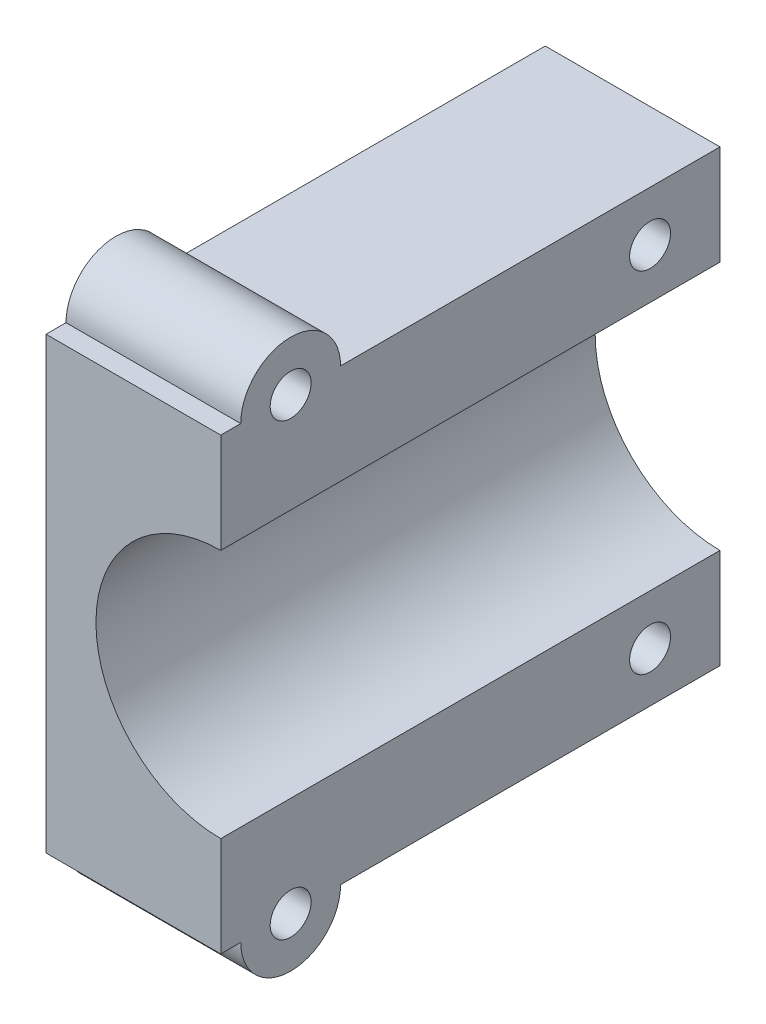
SolidWorks part; units mm, degrees
material "PLA"
ref_plane "Front Plane" through (0, 0, 0) normal (0, 0, 1) x (1, 0, 0)
ref_plane "Top Plane" through (0, 0, 0) normal (0, 1, 0) x (1, 0, 0)
ref_plane "Right Plane" through (0, 0, 0) normal (1, 0, 0) x (0, 0, -1)
sketch "Sketch1" plane through (0, 0, 0) normal (0, 0, 1) x (1, 0, 0)
  line L0 (-17.5, 22.5) -> (-17.5, 0)
  line L1 (55, 0) -> (-55, 0) construction
  line L2 (-17.5, 0) -> (17.5, 0)
  line L3 (17.5, 0) -> (17.5, 22.5)
  line L4 (-17.5, 22.5) -> (-12.5, 22.5)
  line L5 (17.5, 22.5) -> (12.5, 22.5)
  line L6 (0, -44.7868) -> (0, 44.7868) construction
  arc A0 (-12.5, 22.5) -> (12.5, 22.5) centre (0, 22.5) ccw
  dimension "D1" = 12.5
  dimension "D2" = 22.5
  dimension "D3" = 5
extrude "Boss-Extrude1" add sketch "Sketch1" along normal mid plane 50
sketch "Construct1" plane through (0, 0, 0) normal (0, 1, 0) x (1, 0, 0)
  line L0 (17.5, 0) -> (43.4808, -15) construction
  line L1 (-44.2539, 0) -> (44.2539, 0) construction
  line L2 (34.7051, -0.1998) -> (26.2756, -14.8002) construction
  line L3 (17.5, -25) -> (17.5, 25) construction
  point P6 (30.4904, -7.5)
  point P7 (30.4904, -7.5)
  dimension "D1" = 30
  dimension "D2" = 15
ref_plane "LegBuildPlane" through (26.1154, 0, 15.0777) normal (0.866, 0, 0.5) x (0.5, 0, -0.866)
sketch "Sketch5" plane through (26.1154, 0, 15.0777) normal (0.866, 0, 0.5) x (0.5, 0, -0.866)
  line L0 (-8.7, 22.5) -> (-3.75, 22.5)
  line L1 (21.25, 22.5) -> (26.2, 22.5)
  line L2 (17.1795, 0) -> (0.3205, 0) construction
  arc A0 (-3.75, 22.5) -> (21.25, 22.5) centre (8.75, 22.5) ccw
  arc A1 (-8.7, 22.5) -> (26.2, 22.5) centre (8.75, 22.5) ccw
  point P9 (8.75, 0)
  dimension "D1" = 17.45
  dimension "D2" = 12.5
  dimension "D3" = 22.5
  dimension "D4" = 0
extrude "Boss-Extrude2" add sketch "Sketch5" against normal up to surface and the other way blind 30 up to face at (17.5, 11.25, 0)
sketch "Sketch9" plane through (-17.5, 0, 0) normal (-1, 0, 0) x (0, 0, 1)
  line L2 (55, 0) -> (-55, 0) construction
  line L3 (-25, 22.5) -> (-25, 0) construction
  circle A0 centre (-18, 5) radius 2.05
  dimension "D1" = 4.1
  dimension "D2" = 5
  dimension "D3" = 7
extrude "Cut-Extrude3" cut sketch "Sketch9" against normal up to surface (35 mm away) up to face at (17.5, 12.0917, 0)
sketch "Construct2" plane through (0, 22.5, 0) normal (0, 1, 0) x (1, 0, 0)
  line L0 (20.0981, -15.9338) -> (32.5981, 5.7169) construction
  line L2 (50.2211, -33.3253) -> (17.5, -14.4338) construction
  line L3 (62.7211, -11.6747) -> (17.5, 14.4338) construction
  line L4 (17.5, 0) -> (26.3481, -5.1084) construction
  line L11 (-44.2539, 0) -> (44.2539, 0) construction
  dimension "D1" = 3
  dimension "D2" = 90
ref_plane "LegBuildPlane2" through (21.9731, 0, 12.6862) normal (0.866, 0, 0.5) x (0.5, 0, -0.866)
sketch "Sketch12" plane through (21.9731, 0, 12.6862) normal (0.866, 0, 0.5) x (0.5, 0, -0.866)
  line L0 (-3.75, 22.5) -> (21.25, 22.5)
  arc A0 (-3.75, 22.5) -> (21.25, 22.5) centre (8.75, 22.5) ccw
extrude "Boss-Extrude5" add sketch "Sketch12" against normal up to surface (17.4338 mm away) up to face at (17.5, 16.25, 0)
mirror "Mirror1" about plane through (17.5, 22.5, 25) normal (0, -1, 0) of "Boss-Extrude2", "Boss-Extrude1", "Cut-Extrude3", "Boss-Extrude5"
sketch "Sketch13" plane through (0, 0, 0) normal (0, 1, 0) x (1, 0, 0)
  line L0 (17.5, 0) -> (43.4808, -15) construction
  line L1 (47.7461, -37.6121) -> (65.1961, -7.3879) construction
  circle A0 centre (43.4808, -15) radius 1.55
  dimension "D2" = 3.1
  dimension "D1" = 15
extrude "Cut-Extrude4" cut sketch "Sketch13" along normal through all
sketch "Sketch16" plane through (0, 0, 0) normal (1, 0, 0) x (0, 0, -1)
  line L1 (25, 45) -> (-38, 45)
  line L2 (25, 45) -> (25, 0)
  line L3 (25, 0) -> (-38, 0)
  line L4 (-38, 45) -> (-38, 0)
  line L7 (55, 0) -> (-55, 0) construction
  line L8 (0, 44.2539) -> (0, -44.2539) construction
  dimension "D1" = 38
extrude "Cut-Extrude5" cut sketch "Sketch16" along normal up to surface (83.8953 mm away) up to face at (65.1961, 22.5, 7.3879)
sketch "Sketch17" plane through (-17.5, 0, 0) normal (-1, 0, 0) x (0, 0, 1)
  line L0 (55, 0) -> (-55, 0) construction
  line L1 (13, 0) -> (23, 0)
  arc A0 (13, 0) -> (23, 0) centre (18, 0) ccw
  circle A1 centre (-18, 5) radius 2.05 construction
  dimension "D2" = 5
  dimension "D1" = 36
extrude "Boss-Extrude6" add sketch "Sketch17" against normal blind 17.5
sketch "Sketch18" plane through (-17.5, 0, 0) normal (-1, 0, 0) x (0, 0, 1)
  circle A0 centre (18, 0) radius 2.05
  dimension "D1" = 4.1
extrude "Cut-Extrude6" cut sketch "Sketch18" against normal up to surface (17.5 mm away) up to face at (0, 5, -15.95)
ref_plane "HolePlane" through (0, 22.5, 0) normal (0, 1, 0) x (1, 0, 0)
mirror "Mirror2" about plane through (0, 22.5, 0) normal (0, 1, 0) of "Boss-Extrude6", "Cut-Extrude6"
equation "\"TubeDiam\"= 12.5"
equation "\"D1@Sketch1\"=\"TubeDiam\""
equation "\"D2@Sketch1\"=\"ClampHeight\""
equation "\"MountLength\"= 50"
equation "\"D1@Boss-Extrude1\"=\"MountLength\""
equation "\"MountHoleSize\"=3.1"
equation "\"LipWidth\"= 5"
equation "\"D3@Sketch1\"=\"LipWidth\""
equation "\"LegDiam\"= 12.5"
equation "\"LegThickness\" = \"TubeDiam\" + 4.95"
equation "\"D1@Sketch5\"=\"LegThickness\""
equation "\"D2@Sketch5\"=\"TubeDiam\""
equation "\"ClampHeight\" = \"TubeDiam\" + 10"
equation "\"D3@Sketch5\"=\"ClampHeight\""
equation "\"HubHoleDist\"=7"
equation "\"HubHoleSize\"=4.1"
equation "\"D2@Sketch13\"=\"MountHoleSize\""
equation "\"D1@Sketch9\"=\"HubHoleSize\""
equation "\"D3@Sketch9\"=\"HubHoleDist\""
equation "\"D1@Sketch17\"=\"MountLength\" - 2 * \"HubHoleDist\""
equation "\"D1@Boss-Extrude6\"=\"TubeDiam\"+5"
equation "\"D1@Sketch18\"=\"HubHoleSize\""
